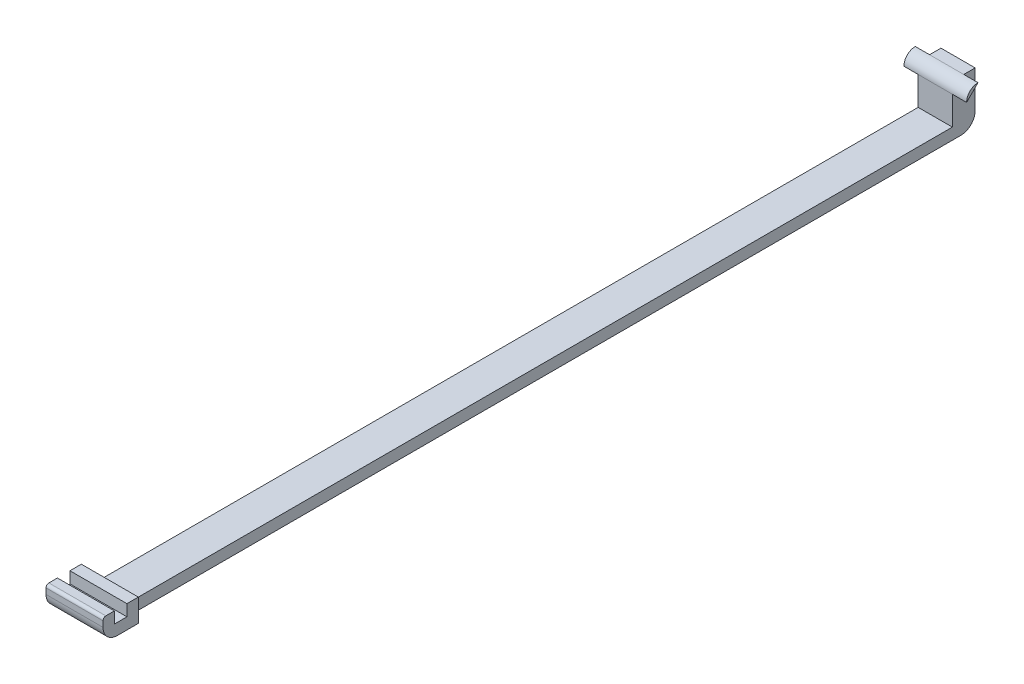
SolidWorks part; units mm, degrees
ref_plane "Front Plane" through (0, 0, 0) normal (0, 0, 1) x (1, 0, 0)
ref_plane "Top Plane" through (0, 0, 0) normal (0, 1, 0) x (1, 0, 0)
ref_plane "Right Plane" through (0, 0, 0) normal (1, 0, 0) x (0, 0, -1)
sketch "Sketch1" plane through (0, 0, 0) normal (0, 1, 0) x (1, 0, 0)
  line L1 (-19.5, 77.5) -> (19.5, 77.5)
  line L2 (-19.5, 77.5) -> (-19.5, -77.5)
  line L3 (-19.5, -77.5) -> (19.5, -77.5)
  line L4 (19.5, 77.5) -> (19.5, -77.5)
  line L5 (-19.5, 77.5) -> (19.5, -77.5) construction
  line L6 (-19.5, -77.5) -> (19.5, 77.5) construction
  point P0 (0, 0)
  dimension "D1" = 39
  dimension "D2" = 155
extrude "Boss-Extrude1" add sketch "Sketch1" along normal blind 2
sketch "Sketch2" plane through (0, 2, 0) normal (0, 1, 0) x (1, 0, 0)
  line L0 (-17.5, -75.5) -> (-17.5, -77.5)
  line L1 (-19.5, 77.5) -> (19.5, 77.5)
  line L2 (-19.5, 77.5) -> (-19.5, -77.5)
  line L3 (-19.5, -77.5) -> (19.5, -77.5)
  line L4 (19.5, 77.5) -> (19.5, -77.5)
  line L5 (-17.5, 75.5) -> (17.5, 75.5)
  line L6 (-17.5, 75.5) -> (-17.5, -75.5)
  line L7 (-17.5, -75.5) -> (17.5, -75.5)
  line L8 (17.5, 75.5) -> (17.5, -75.5)
  line L9 (-17.5, 75.5) -> (17.5, -75.5) construction
  line L10 (-17.5, -75.5) -> (17.5, 75.5) construction
  line L11 (17.5, -75.5) -> (17.5, -77.5)
  point P6 (0, 0)
  line M9 (19.5, -77.5) -> (19.5, 77.5)
  line M10 (19.5, 77.5) -> (-19.5, 77.5)
  line M11 (-19.5, 77.5) -> (-19.5, -77.5)
  line M12 (-19.5, -77.5) -> (19.5, -77.5)
  dimension "D1" = 2
  dimension "D2" = 2
extrude "Boss-Extrude2" add sketch "Sketch2" along normal blind 38 contours L8 L11 L3 L0 L6 L5 M9 M10 M11 M12 region at (-19.0983, 2, 76.5)
sketch "Sketch3" plane through (0, 2, 0) normal (0, 1, 0) x (1, 0, 0)
  line L0 (-17.5, 75.5) -> (-17.5, -77.5) construction
  line L1 (-17.5, -77.5) -> (-15.5, -77.5)
  line L2 (-17.5, -77.5) -> (-17.5, -75.5)
  line L3 (-17.5, -75.5) -> (-15.5, -75.5)
  line L4 (-15.5, -77.5) -> (-15.5, -75.5)
  line L5 (-17.5, -73.3) -> (-15.5, -73.3)
  line L6 (-17.5, -73.3) -> (-17.5, -71.3)
  line L7 (-17.5, -71.3) -> (-15.5, -71.3)
  line L8 (-15.5, -73.3) -> (-15.5, -71.3)
  line L9 (17.5, 75.5) -> (17.5, -77.5) construction
  line L10 (17.5, -77.5) -> (15.5, -77.5)
  line L11 (17.5, -77.5) -> (17.5, -75.5)
  line L12 (17.5, -75.5) -> (15.5, -75.5)
  line L13 (15.5, -77.5) -> (15.5, -75.5)
  line L14 (17.5, -73.3) -> (15.5, -73.3)
  line L15 (17.5, -73.3) -> (17.5, -71.3)
  line L16 (17.5, -71.3) -> (15.5, -71.3)
  line L17 (15.5, -73.3) -> (15.5, -71.3)
  line L18 (15.5, -75.5) -> (15.5, -73.3) construction
  line L19 (-15.5, -73.3) -> (15.5, -73.3) construction
  line L20 (-15.5, -75.5) -> (-15.5, -73.3) construction
  line L21 (-15.5, -75.5) -> (15.5, -75.5) construction
  line L22 (15.5, -71.3) -> (-15.5, -71.3) construction
  dimension "D1" = 2
  dimension "D2" = 2
  dimension "D3" = 2.2
  dimension "D4" = 2
extrude "Boss-Extrude3" add sketch "Sketch3" along normal up to surface (38 mm away) up to face at (0, 40, 0.5)
sketch "Sketch4" plane through (0, 0, -75.5) normal (0, 0, 1) x (1, 0, 0)
  line L0 (-17.5, 40) -> (-15.5, 40)
  line L1 (-17.5, 40) -> (17.5, 40) construction
  line L2 (-15.5, 40) -> (-15.5, 38)
  line L3 (-15.5, 38) -> (-17.5, 38)
  line L5 (-17.5, 38) -> (-17.5, 40)
  line L7 (-17.5, 40) -> (-17.5, 2) construction
  line L8 (-15.5, 33.8) -> (-17.5, 31.8)
  line L9 (-17.5, 31.8) -> (-17.5, 35.8)
  line L10 (-15.5, 33.8) -> (-15.5, 35.8)
  line L11 (-15.5, 35.8) -> (-17.5, 35.8)
  line L12 (0, 0) -> (0, 40) construction
  line L13 (15.5, 35.8) -> (17.5, 35.8)
  line L14 (15.5, 33.8) -> (15.5, 35.8)
  line L15 (17.5, 31.8) -> (17.5, 35.8)
  line L16 (15.5, 33.8) -> (17.5, 31.8)
  line L17 (17.5, 38) -> (17.5, 40)
  line L18 (15.5, 38) -> (17.5, 38)
  line L19 (15.5, 40) -> (15.5, 38)
  line L20 (17.5, 40) -> (15.5, 40)
  dimension "D1" = 2
  dimension "D2" = 2
  dimension "D3" = 45
  dimension "D4" = 2.2
  dimension "D5" = 2
extrude "Boss-Extrude4" add sketch "Sketch4" along normal up to surface (153 mm away) up to face at (0, 20.5, 77.5)
sketch "Sketch5" plane through (0, 2, 0) normal (0, 1, 0) x (1, 0, 0)
  line L1 (-15.5, -77.5) -> (15.5, -77.5)
  line L2 (-15.5, -77.5) -> (-15.5, -75.5)
  line L3 (-15.5, -75.5) -> (15.5, -75.5)
  line L4 (15.5, -77.5) -> (15.5, -75.5)
  line L5 (-15.5, -71.3) -> (15.5, -71.3)
  line L6 (-15.5, -71.3) -> (-15.5, -73.3)
  line L7 (-15.5, -73.3) -> (15.5, -73.3)
  line L8 (15.5, -71.3) -> (15.5, -73.3)
sketch "Sketch6" plane through (0, 0, -75.5) normal (0, 0, 1) x (1, 0, 0)
  line L0 (-17.5, 38) -> (-15.5, 38) construction
  line L1 (-17.5, 38) -> (17.5, 38)
  line L2 (-17.5, 38) -> (-17.5, 35.8)
  line L3 (-17.5, 35.8) -> (17.5, 35.8)
  line L4 (17.5, 38) -> (17.5, 35.8)
  line L5 (-17.5, 38) -> (-17.5, 35.8) construction
  line L6 (-15.5, 35.8) -> (-17.5, 35.8) construction
extrude "Cut-Extrude1" cut sketch "Sketch6" along normal through all
sketch "Sketch7" plane through (0, 2, 0) normal (0, 1, 0) x (1, 0, 0)
  line L1 (-17.5, -75.5) -> (17.5, -75.5)
  line L2 (-17.5, -75.5) -> (-17.5, -73.3)
  line L3 (-17.5, -73.3) -> (17.5, -73.3)
  line L4 (17.5, -75.5) -> (17.5, -73.3)
extrude "Cut-Extrude2" cut sketch "Sketch7" along normal through all
extrude "Boss-Extrude5" add sketch "Sketch5" along normal blind 2
sketch "Sketch8" plane through (0, 0, 0) normal (1, 0, 0) x (0, 0, -1)
  line L0 (75.5, 40) -> (73.5, 40)
  line L1 (-73.3, 40) -> (75.5, 40) construction
  line L2 (73.5, 40) -> (73.5, 38)
  line L3 (-73.3, 38) -> (75.5, 38) construction
  line L4 (73.5, 38) -> (75.5, 38)
  line L5 (75.5, 38) -> (75.5, 40)
  line L6 (75.5, 35.8) -> (73.5, 35.8)
  line L7 (-73.3, 35.8) -> (75.5, 35.8) construction
  line L8 (73.5, 35.8) -> (73.5, 33.8)
  line L9 (-71.3, 33.8) -> (75.5, 33.8) construction
  line L10 (73.5, 33.8) -> (75.5, 31.8)
  line L11 (75.5, 31.8) -> (75.5, 35.8)
  dimension "D1" = 2
extrude "Boss-Extrude6" add sketch "Sketch8" along normal up to surface and the other way up to surface up to face at (17.5, 16.9, -2.1) other way up to face at (-17.5, 16.9, -2.1)
sketch "Sketch10" plane through (-17.5, 0, 0) normal (1, 0, 0) x (0, 0, -1)
  line L1 (-75.5, 35.8) -> (-77.5, 35.8)
  line L2 (-75.5, 35.8) -> (-75.5, 38)
  line L3 (-75.5, 38) -> (-77.5, 38)
  line L4 (-77.5, 35.8) -> (-77.5, 38)
  line L5 (-73.3, 40) -> (-75.5, 40)
  line L6 (-73.3, 40) -> (-73.3, 38)
  line L7 (-73.3, 38) -> (-75.5, 38)
  line L8 (-75.5, 40) -> (-75.5, 38)
  line M1 (-75.5, 40) -> (-75.5, 38)
  line M2 (-75.5, 38) -> (-77.5, 38)
  line M3 (-77.5, 38) -> (-77.5, 35.8)
  line M4 (-77.5, 35.8) -> (-75.5, 35.8)
  line M11 (-73.3, 38) -> (-73.3, 40)
  line M12 (-73.3, 40) -> (-75.5, 40)
extrude "Boss-Extrude8" add sketch "Sketch10" along normal up to surface (2 mm away) contours L2 M4 M2 M3 | L7 M11 M12 M1 region at (-17.5, 39, 74.4) region at (-17.5, 36.9, 76.5) up to face at (-15.5, 39, -0.1)
sketch "Sketch11" plane through (17.5, 0, 0) normal (-1, 0, 0) x (0, 0, 1)
  line L1 (75.5, 35.8) -> (77.5, 35.8)
  line L2 (75.5, 35.8) -> (75.5, 38)
  line L3 (75.5, 38) -> (77.5, 38)
  line L4 (77.5, 35.8) -> (77.5, 38)
  line L5 (73.3, 40) -> (75.5, 40)
  line L6 (73.3, 40) -> (73.3, 38)
  line L7 (73.3, 38) -> (75.5, 38)
  line L8 (75.5, 40) -> (75.5, 38)
  line M2 (75.5, 35.8) -> (77.5, 35.8)
  line M3 (77.5, 35.8) -> (77.5, 38)
  line M4 (77.5, 38) -> (75.5, 38)
  line M5 (75.5, 38) -> (75.5, 40)
  line M6 (75.5, 40) -> (73.3, 40)
  line M7 (73.3, 40) -> (73.3, 38)
extrude "Boss-Extrude9" add sketch "Sketch11" along normal up to surface (2 mm away) contours L2 M2 M3 M4 | L7 M7 M5 M6 region at (17.5, 36.9, 76.5) region at (17.5, 39, 74.4) up to face at (15.5, 39, -0.1)
fillet "Fillet2" radius 2.5 17 edges at (-17.5, 16.9, 71.3) (17.5, 16.9, 71.3) (19.5, 20, 77.5) (-19.5, 20, 77.5) (-19.5, 20, -77.5) (-17.5, 16.9, -75.5) (17.5, 16.9, -75.5) (19.5, 20, -77.5) (-19.5, 40, 0) (0, 40, -77.5) (19.5, 40, 0) (0, 0, -77.5) (0, 0, 77.5) (-19.5, 0, 0) (19.5, 0, 0) (-17.5, 40, 77.5) (17.5, 40, 77.5)
sketch "Sketch13" plane through (0, 0, -77.5) normal (0, 0, -1) x (-1, 0, 0)
  line L0 (15.5, 37.5) -> (15.5, 4) construction
  line L1 (-15.5, 7) -> (15.5, 7)
  line L2 (-15.5, 7) -> (-15.5, 4)
  line L3 (-15.5, 4) -> (15.5, 4)
  line L4 (15.5, 7) -> (15.5, 4)
  dimension "D1" = 3
sketch "Sketch14" plane through (0, 0, -75.5) normal (0, 0, 1) x (1, 0, 0)
  line L1 (-18.25, 9) -> (18.25, 9)
  line L2 (-18.25, 9) -> (-18.25, 1.25)
  line L3 (-18.25, 1.25) -> (18.25, 1.25)
  line L4 (18.25, 9) -> (18.25, 1.25)
  line L5 (15.5, 7) -> (-15.5, 7) construction
  line L7 (17, 0) -> (17, 2.5) construction
  line L8 (19.5, 2.5) -> (17, 2.5) construction
  line L10 (-19.5, 2.5) -> (-17, 2.5) construction
  point P20 (17, 1.25)
  point P23 (18.25, 2.5)
  point P26 (-18.25, 2.5)
  dimension "D1" = 2
extrude "Boss-Extrude10" add sketch "Sketch14" along normal blind 2
extrude "Cut-Extrude4" cut sketch "Sketch13" against normal blind 2
fillet "Fillet3" radius 2 1 edges at (0, 9, -73.5)
fillet "Fillet4" radius 0.5 12 edges at (0, 4, -77.5) (0, 7, -77.5) (15.5, 7, -76.5) (15.5, 4, -76.5) (15.5, 5.5, -77.5) (-15.5, 4, -76.5) (-15.5, 7, -76.5) (-15.5, 5.5, -77.5) (0, 7, -75.5) (-15.5, 5.5, -75.5) (0, 4, -75.5) (15.5, 5.5, -75.5)
sketch "Sketch15" plane through (0, 0, 0) normal (0, -1, 0) x (1, 0, 0)
  line L0 (0, 77.5) -> (0, 0) construction
  line L1 (-17, 77.5) -> (17, 77.5) construction
  line L2 (0, 0) -> (0, -77.5) construction
  line L4 (17, -77.5) -> (-17, -77.5) construction
  circle A0 centre (0, 38.75) radius 5.1
  circle A1 centre (0, -38.75) radius 5.1
  dimension "D1" = 10.2
extrude "Cut-Extrude5" cut sketch "Sketch15" against normal through all
sketch "Sketch16" plane through (0, 2, 0) normal (0, 1, 0) x (1, 0, 0)
  circle A0 centre (0, 38.75) radius 7.1
  circle A1 centre (0, -38.75) radius 7.1
  circle A2 centre (0, 38.75) radius 5.1 construction
  dimension "D1" = 2
extrude "Boss-Extrude11" add sketch "Sketch16" along normal blind 1
fillet "Fillet5" radius 0.5 4 edges at (0, 2, 45.85) (0, 2, -31.65) (0, 3, 45.85) (0, 3, -31.65)
sketch "Sketch12" plane through (0, 0, -75.5) normal (0, 0, 1) x (1, 0, 0)
  line L0 (0, 0) -> (0, 40) construction
  line L1 (15.5, 40) -> (-15.5, 40) construction
  line L2 (0, 20) -> (-10, 20)
  line L3 (0, 20) -> (-9.0097, 15.6612)
  line L4 (0, 20) -> (-6.2349, 12.1817)
  line L5 (0, 20) -> (-2.2252, 10.2507)
  line L6 (0, 20) -> (2.2252, 10.2507)
  line L7 (0, 20) -> (6.2349, 12.1817)
  line L8 (0, 20) -> (9.0097, 15.6612)
  line L9 (0, 20) -> (10, 20)
  line L10 (0, 20) -> (9.0097, 24.3388)
  line L11 (0, 20) -> (6.2349, 27.8183)
  line L12 (0, 20) -> (2.2252, 29.7493)
  line L13 (0, 20) -> (-2.2252, 29.7493)
  line L14 (0, 20) -> (-6.2349, 27.8183)
  line L15 (0, 20) -> (-9.0097, 24.3388)
  circle A0 centre (0, 20) radius 10
  circle A1 centre (0, 20) radius 7.5
  circle A2 centre (0, 20) radius 5
  circle A3 centre (0, 20) radius 2.5
  point P26 (0, 20)
  dimension "D1" = 20
  dimension "D2" = 2.5
  dimension "D3" = 2.5
  dimension "D4" = 2.5
  dimension "D5" = 14
extrude "Cut-Extrude3" cut sketch "Sketch12" against normal through all contours A1 L6 A0 L7 | A1 L4 A0 L5 | A1 L2 A0 L3 | A1 L14 A0 L15 | A1 L0 A0 L13 | L0 A1 L12 A0 | A1 L10 A0 L11 | A1 L8 A0 L9 | A3 L8 A2 L9 | A3 L10 A2 L11 | L0 A3 L12 A2 | A3 L0 A2 L13 | A3 L14 A2 L15 | A3 L2 A2 L3 | A3 L4 A2 L5 | A3 L6 A2 L7 region at (-3.7903, 12.1293, -75.5) region at (3.7903, 12.1293, -75.5) region at (-1.6732, 16.5256, -75.5) region at (1.6732, 16.5256, -75.5) region at (-8.5168, 18.0561, -75.5) region at (8.5168, 18.0561, -75.5) region at (-0.4345, 23.8563, -75.5) region at (0.4345, 23.8563, -75.5) region at (-3.7596, 19.1419, -75.5) region at (3.7596, 19.1419, -75.5) region at (3.015, 22.4044, -75.5) region at (-3.015, 22.4044, -75.5) region at (-6.8299, 25.4467, -75.5) region at (6.8299, 25.4467, -75.5) region at (-0.9843, 28.7358, -75.5) region at (0.9843, 28.7358, -75.5)
fillet "Fillet6" radius 0.4 112 edges at (5.4555, 26.841, -77.5) (7.8183, 26.2349, -77.5) (7.8835, 23.7965, -77.5) (5.8637, 24.6762, -77.5) (3.75, 20, -77.5) (4.8746, 18.8874, -77.5) (3.3786, 18.3729, -77.5) (2.4373, 19.4437, -77.5) (-1.9471, 28.5306, -77.5) (0, 30, -77.5) (1.9471, 28.5306, -77.5) (0, 27.5, -77.5) (-7.8835, 16.2035, -77.5) (-9.7493, 17.7748, -77.5) (-8.75, 20, -77.5) (-7.312, 18.3311, -77.5) (2.3381, 17.0681, -77.5) (2.1694, 15.4952, -77.5) (0.8345, 16.344, -77.5) (1.0847, 17.7476, -77.5) (-0.8345, 16.344, -77.5) (-2.1694, 15.4952, -77.5) (-2.3381, 17.0681, -77.5) (-1.0847, 17.7476, -77.5) (5.4555, 13.159, -77.5) (4.3388, 10.9903, -77.5) (1.9471, 11.4694, -77.5) (3.2541, 13.2427, -77.5) (0, 22.5, -77.5) (-0.8345, 23.656, -77.5) (0, 25, -77.5) (0.8345, 23.656, -77.5) (-3.3786, 21.6271, -77.5) (-3.9092, 23.1174, -77.5) (-2.3381, 22.9319, -77.5) (-1.9546, 21.5587, -77.5) (-3.3786, 18.3729, -77.5) (-4.8746, 18.8874, -77.5) (-3.75, 20, -77.5) (-2.4373, 19.4437, -77.5) (-1.9471, 11.4694, -77.5) (-4.3388, 10.9903, -77.5) (-5.4555, 13.159, -77.5) (-3.2541, 13.2427, -77.5) (-7.8835, 23.7965, -77.5) (-7.8183, 26.2349, -77.5) (-5.4555, 26.841, -77.5) (-5.8637, 24.6762, -77.5) (2.3381, 22.9319, -77.5) (3.9092, 23.1174, -77.5) (3.3786, 21.6271, -77.5) (1.9546, 21.5587, -77.5) (8.75, 20, -77.5) (9.7493, 17.7748, -77.5) (7.8835, 16.2035, -77.5) (7.312, 18.3311, -77.5) (7.8835, 23.7965, -75.5) (7.8183, 26.2349, -75.5) (5.4555, 26.841, -75.5) (5.8637, 24.6762, -75.5) (3.3786, 18.3729, -75.5) (4.8746, 18.8874, -75.5) (3.75, 20, -75.5) (2.4373, 19.4437, -75.5) (1.9471, 28.5306, -75.5) (0, 30, -75.5) (-1.9471, 28.5306, -75.5) (0, 27.5, -75.5) (-8.75, 20, -75.5) (-9.7493, 17.7748, -75.5) (-7.8835, 16.2035, -75.5) (-7.312, 18.3311, -75.5) (0.8345, 16.344, -75.5) (2.1694, 15.4952, -75.5) (2.3381, 17.0681, -75.5) (1.0847, 17.7476, -75.5) (-2.3381, 17.0681, -75.5) (-2.1694, 15.4952, -75.5) (-0.8345, 16.344, -75.5) (-1.0847, 17.7476, -75.5) (1.9471, 11.4694, -75.5) (4.3388, 10.9903, -75.5) (5.4555, 13.159, -75.5) (3.2541, 13.2427, -75.5) (0, 22.5, -75.5) (0.8345, 23.656, -75.5) (0, 25, -75.5) (-0.8345, 23.656, -75.5) (-2.3381, 22.9319, -75.5) (-3.9092, 23.1174, -75.5) (-3.3786, 21.6271, -75.5) (-1.9546, 21.5587, -75.5) (-3.75, 20, -75.5) (-4.8746, 18.8874, -75.5) (-3.3786, 18.3729, -75.5) (-2.4373, 19.4437, -75.5) (-5.4555, 13.159, -75.5) (-4.3388, 10.9903, -75.5) (-1.9471, 11.4694, -75.5) (-3.2541, 13.2427, -75.5) (-5.4555, 26.841, -75.5) (-7.8183, 26.2349, -75.5) (-7.8835, 23.7965, -75.5) (-5.8637, 24.6762, -75.5) (3.3786, 21.6271, -75.5) (3.9092, 23.1174, -75.5) (2.3381, 22.9319, -75.5) (7.8835, 16.2035, -75.5) (9.7493, 17.7748, -75.5) (8.75, 20, -75.5) (7.312, 18.3311, -75.5) (1.9546, 21.5587, -75.5)
fillet "Fillet7" radius 0.5 8 edges at (15.5, 40, 0.75) (15.5, 39.2678, 76.7678) (-15.5, 40, 0.75) (-15.5, 39.2678, 76.7678) (0, 40, -73.5) (15.5, 20.75, 77.5) (-15.5, 20.75, 77.5) (0, 4, 77.5)
sketch "Sketch20" plane through (0, 0, 0) normal (1, 0, 0) x (0, 0, -1)
  line L1 (75.5, 9) -> (77.5, 9)
  line L2 (77.5, 2.5) -> (77.5, 37.5) construction
  line L3 (77.5, 9) -> (77.5, 0)
  line L4 (77.5, 0) -> (-77.5, 0)
  line L5 (-77.5, 0) -> (-77.5, 4)
  line L6 (-75.5, 4) -> (-77.5, 4)
  line L7 (-75.5, 4) -> (73.5, 4)
  line L8 (73.5, 2) -> (73.5, 7) construction
  line L9 (73.5, 4) -> (73.5, 9)
  line L10 (73.5, 9) -> (75.5, 9)
  line L11 (-77.5, 4) -> (-77.5, 40)
  line L12 (-77.5, 40) -> (77.5, 40)
  line L13 (77.5, 40) -> (77.5, 9)
  dimension "D1" = 40
extrude "Cut-Extrude8" cut sketch "Sketch20" against normal through all both and the other way through all contours L13 L12 L11 L6 L7 L9 L10 L1 region at (0, 22.0558, 0.2716)
sketch "Sketch21" plane through (0, 0, 0) normal (0, 1, 0) x (1, 0, 0)
  line L0 (17, 77.5) -> (17, 73.5)
  line L1 (17, 77.5) -> (17, 75) construction
  line L4 (-17.4495, 73.5) -> (17.4495, 73.5) construction
  line L9 (17, -77.5) -> (19.5, -77.5)
  line L10 (19.5, -77.5) -> (19.5, 77.5)
  line L11 (19.5, 77.5) -> (17, 77.5)
  line L12 (19.5, 73.5) -> (19.5, -75) construction
  line L13 (16, -77.5) -> (17, -77.5) construction
  line L14 (0, 0) -> (0, -71.3) construction
  line L15 (15, -71.3) -> (-15, -71.3) construction
  line L24 (17, 73.5) -> (17, -77.5)
  line L25 (-17, 73.5) -> (-17, -77.5)
  line L26 (-19.5, 77.5) -> (-17, 77.5)
  line L27 (-19.5, -77.5) -> (-19.5, 77.5)
  line L28 (-17, -77.5) -> (-19.5, -77.5)
  line L29 (-17, 77.5) -> (-17, 73.5)
  line L30 (-17, -77.5) -> (17, -77.5)
  line L31 (-17, 77.5) -> (17, 77.5)
  arc A0 (19.5, 75) -> (17, 77.5) centre (17, 75) ccw construction
extrude "Cut-Extrude11" cut sketch "Sketch21" along normal through all contours L0 L24 L9 L10 L11 | L29 L26 L27 L28 L25 region at (18.25, 0, 0) region at (-18.25, 0, 0)
sketch "Sketch24" plane through (0, 0, 0) normal (0, 1, 0) x (1, 0, 0)
  line L9 (17, -77.5) -> (15, -77.5)
  line L10 (16, -77.5) -> (-16, -77.5) construction
  line L11 (15, -77.5) -> (15, -71.3)
  line L12 (15, -71.3) -> (17, -70.3)
  line L13 (17, -70.3) -> (17, -77.5)
  line L14 (0, 0) -> (0, -31.15) construction
  line L15 (-17, -70.3) -> (-17, -77.5)
  line L16 (-15, -71.3) -> (-17, -70.3)
  line L17 (-15, -77.5) -> (-15, -71.3)
  line L18 (-17, -77.5) -> (-15, -77.5)
  circle A1 centre (0, -38.75) radius 7.6 construction
extrude "Cut-Extrude12" cut sketch "Sketch24" along normal through all
sketch "Sketch26" plane through (17, 0, 0) normal (1, 0, 0) x (0, 0, -1)
  line L0 (75.5, 9) -> (73.5, 7)
  line L1 (77.5, 9) -> (74.5, 9) construction
  line L2 (73.5, 7) -> (73.5, 9)
  line L3 (73.5, 9) -> (75.5, 9)
extrude "Cut-Extrude13" cut sketch "Sketch26" against normal blind 2.5
mirror "Mirror1" about plane through (0, 0, 0) normal (1, 0, 0) of "Cut-Extrude13"
sketch "Sketch27" plane through (0, 0, 0) normal (0, -1, 0) x (1, 0, 0)
  circle A0 centre (0, 38.75) radius 5.1
  circle A1 centre (0, -38.75) radius 5.1
  circle A2 centre (0, -38.75) radius 5.1 construction
  circle A3 centre (0, 38.75) radius 5.1 construction
extrude "Boss-Extrude12" add sketch "Sketch27" against normal up to surface (2 mm away) up to face at (0, 2, 46.35)
sketch "Sketch29" plane through (0, 0, 0) normal (1, 0, 0) x (0, 0, -1)
  line L0 (-70.3, 2) -> (73.5, 2) construction
  line L1 (-46.35, 2) -> (46.35, 2)
  line L2 (-46.35, 2) -> (-46.35, 3)
  line L3 (-46.35, 3) -> (46.35, 3)
  line L4 (46.35, 2) -> (46.35, 3)
  line L5 (45.35, 3) -> (32.15, 3) construction
extrude "Cut-Extrude14" cut sketch "Sketch29" against normal through all both and the other way through all
sketch "Sketch30" plane through (0, 0, 0) normal (0, 1, 0) x (1, 0, 0)
  line L0 (-17, 77.5) -> (17, 77.5) construction
  line L1 (-14.5, -77.5) -> (14.5, -77.5)
  line L2 (-14.5, -77.5) -> (-14.5, 77.5)
  line L3 (-14.5, 77.5) -> (14.5, 77.5)
  line L4 (14.5, -77.5) -> (14.5, 77.5)
  line L5 (14.5, 73.5) -> (14.5, 75.5) construction
  line L6 (15, -77.5) -> (-15, -77.5) construction
  line L7 (-14.5, 75.5) -> (-14.5, 73.5) construction
  line L9 (-17, 77.5) -> (17, 77.5)
  line L10 (-17, 77.5) -> (-17, -77.5)
  line L11 (-17, -77.5) -> (17, -77.5)
  line L12 (17, 77.5) -> (17, -77.5)
extrude "Cut-Extrude15" cut sketch "Sketch30" along normal through all contours L10 L11 L2 L9 | L12 L9 L4 L11 region at (-15.75, 0, 0) region at (15.75, 0, 0)
sketch "Sketch31" plane through (0, 0, 0) normal (1, 0, 0) x (0, 0, -1)
  line L0 (77.5, 9) -> (77.5, 7.5) construction
  line L1 (75.5, 8.25) -> (77.5, 8.25)
  line L2 (75.5, 8.25) -> (75.5, 3)
  line L3 (75.5, 3) -> (77.5, 3)
  line L4 (77.5, 8.25) -> (77.5, 3)
  line L5 (75.5, 4.5) -> (75.5, 6.5) construction
  line L6 (77.5, 3.5) -> (77.5, 2.5) construction
extrude "Boss-Extrude13" add sketch "Sketch31" along normal up to surface (14.5 mm away) and the other way up to surface (14.5 mm away) up to face at (14.5, 4.2076, -13.1993) other way up to face at (-14.5, 4.2076, -13.1993)
sketch "Sketch32" plane through (0, 0, 0) normal (0, 1, 0) x (1, 0, 0)
  line L1 (-3, 77.5) -> (-3, -70.3)
  line L3 (3, -70.3) -> (3, 77.5)
  line L5 (14.5, 77.5) -> (-14.5, 77.5)
  line L6 (-3, 0) -> (3, 0) construction
  line L8 (14.5, -77.5) -> (14.5, 77.5)
  line L9 (3, -70.3) -> (5, -71.3)
  line L10 (14.5, -71.3) -> (-14.5, -71.3) construction
  line L11 (-14.5, 77.5) -> (-14.5, -77.5)
  line L14 (-14.5, 77.5) -> (14.5, 77.5) construction
  line L16 (5, -71.3) -> (5, -77.5)
  line L17 (14.5, -77.5) -> (-14.5, -77.5) construction
  line L19 (5, -77.5) -> (14.5, -77.5)
  line L20 (-3, -70.3) -> (-5, -71.3)
  line L22 (-5, -71.3) -> (-5, -77.5)
  line L24 (-5, -77.5) -> (-14.5, -77.5)
  line L29 (-3, -70.3) -> (3, -70.3) construction
  line L30 (14.5, -71.3) -> (-14.5, -71.3) construction
  point P8 (0, 0)
  dimension "D1" = 6
  dimension "D2" = 1
  dimension "D3" = 10
extrude "Cut-Extrude16" cut sketch "Sketch32" along normal through all contours L3 | L1 region at (8.7862, 0, -0.5616) region at (-8.7862, 0, -0.5616)
sketch "Sketch33" plane through (0, 0, 0) normal (1, 0, 0) x (0, 0, -1)
  line L0 (75.5, 9) -> (73.5, 7)
  arc A1 (73.5, 7) -> (75.5, 9) centre (75.5, 7) cw
  arc A2 (75.5, 9) -> (73.5, 7) centre (75.5, 7) ccw construction
extrude "Boss-Extrude14" add sketch "Sketch33" along normal blind 5.5 and the other way blind 5.5
